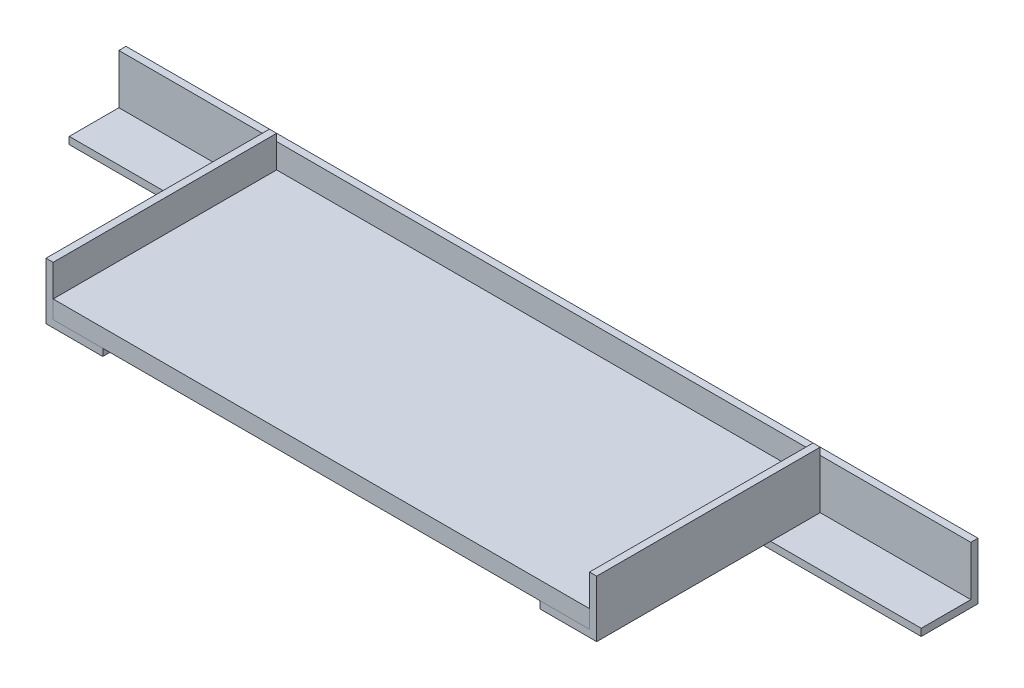
SolidWorks part; units mm, degrees
ref_plane "Front Plane" through (0, 0, 0) normal (0, 0, 1) x (1, 0, 0)
ref_plane "Top Plane" through (0, 0, 0) normal (0, 1, 0) x (1, 0, 0)
ref_plane "Right Plane" through (0, 0, 0) normal (1, 0, 0) x (0, 0, -1)
sketch "Bounding Box" plane through (0, 0, 0) normal (0, 1, 0) x (1, 0, 0)
  line L0 (0, -54.1882) -> (0, 0) construction
  line L1 (100, -179.1882) -> (-100, -179.1882)
  line L2 (100, -179.1882) -> (100, 70.8118)
  line L3 (100, 70.8118) -> (-100, 70.8118)
  line L4 (-100, -179.1882) -> (-100, 70.8118)
  line L5 (100, -179.1882) -> (-100, 70.8118) construction
  line L6 (100, 70.8118) -> (-100, -179.1882) construction
  dimension "D1" = 250
  dimension "D2" = 200
sketch "Sketch2" plane through (0, 0, 0) normal (0, 1, 0) x (1, 0, 0)
  line L4 (0, 39.3098) -> (0, -179.1882) construction
  line L6 (100, -179.1882) -> (-100, -179.1882) construction
  line L8 (-66.6, 34.925) -> (-92, 34.925)
  line L9 (-66.6, 34.925) -> (-66.6, -34.925)
  line L10 (-66.6, -34.925) -> (-92, -34.925)
  line L11 (-92, 34.925) -> (-92, -34.925)
  line L12 (-66.6, 34.925) -> (-92, -34.925) construction
  line L13 (-66.6, -34.925) -> (-92, 34.925) construction
  line L19 (-100, -179.1882) -> (-100, 70.8118) construction
  line L20 (-55.7, 39.3098) -> (-55.7, -40.925)
  line L21 (-60, -68.1179) -> (-60, -118.1179)
  line L22 (-55.7, -40.925) -> (-55, -40.925)
  line L23 (-55, 39.3098) -> (-55, -40.925)
  line L24 (-55, -40.925) -> (-55, -42.925)
  line L25 (-55, -42.925) -> (-96, -42.925)
  line L26 (-96, 47.7081) -> (-96, -50.925)
  line L27 (-91.789, -68.1179) -> (91.789, -68.1179)
  line L28 (-91.789, -68.1179) -> (-91.789, -198.1179)
  line L29 (-91.789, -198.1179) -> (91.789, -198.1179)
  line L30 (91.789, -68.1179) -> (91.789, -198.1179)
  line L31 (-91.789, -68.1179) -> (91.789, -198.1179) construction
  line L32 (-91.789, -198.1179) -> (91.789, -68.1179) construction
  line L33 (-55, 13) -> (-10, 13)
  line L34 (-55, 13) -> (-55, -13)
  line L35 (-55, -13) -> (-10, -13)
  line L36 (-10, 13) -> (-10, -13)
  line L37 (-60, -118.1179) -> (60, -118.1179)
  line L38 (60, -118.1179) -> (60, -68.1179)
  line L41 (-96, -50.925) -> (-100, -50.925)
  line L43 (-96, 47.7081) -> (-100, 47.7081)
  line L44 (-100, 47.7081) -> (-100, -50.925)
  line L45 (-55.7, 0) -> (-10, 0) construction
  line L46 (-95.3, -50.925) -> (-95.3, -42.925)
  line L47 (-96, -50.925) -> (0, -50.925)
  line L48 (-55.7, 39.3098) -> (0, 39.3098)
  line L49 (0, 39.3098) -> (0, -50.925)
  circle A0 centre (74.0462, -90.8108) radius 12.5
  circle A1 centre (-77.6221, -84.4915) radius 12.5
  point P0 (-79.3, 0)
  point P6 (-10, 0)
  point P15 (79.3, 0)
  point P27 (0, -133.1179)
  point P44 (0, -118.1179)
  point P49 (-79.3, 11.3081)
  point P52 (-55, 125)
  dimension "D16" = 25
  dimension "D17" = 45
  dimension "D1" = 69.85
  dimension "D2" = 25.4
  dimension "D3" = 8
  dimension "D4" = 6
  dimension "D5" = 16
  dimension "D6" = 0.7
  dimension "D7" = 4
  dimension "D8" = 2
  dimension "D9" = 120
  dimension "D10" = 0.7
  dimension "D11" = 130
  dimension "D12" = 45
  dimension "D13" = 26
  dimension "D14" = 50
extrude "Platform" add sketch "Sketch2" against normal blind 4 from offset 18 separate body contours L37 L38 L27 L21 region at (0, 0, 93.1179)
sketch "Sketch3" plane through (0, 0, 0) normal (1, 0, 0) x (0, 0, -1)
  line L0 (-68.1179, 23.5) -> (-68.1179, 12.4)
  line L1 (-68.1179, 12.4) -> (-79.2179, 12.4)
  line L2 (-79.2179, 12.4) -> (-79.2179, 10.8)
  line L3 (-79.2179, 10.8) -> (-66.5179, 10.8)
  line L4 (-66.5179, 10.8) -> (-66.5179, 23.5)
  line L5 (-66.5179, 23.5) -> (-68.1179, 23.5)
  line L7 (-68.1179, 14) -> (-68.1179, 18) construction
  line L8 (-118.1179, 14) -> (-68.1179, 14) construction
  dimension "D1" = 1.6
  dimension "D2" = 12.7
  dimension "D3" = 1.6
extrude "Alu Angle Platform Rest" add sketch "Sketch3" along normal mid plane 190.6 separate body
sketch "Drive Axle Holes" plane through (0, 0, 0) normal (1, 0, 0) x (0, 0, -1)
  line L0 (0, 0) -> (0, 50.8) construction
  line L1 (13, 0) -> (-13, 0) construction
  line L2 (10, 50.8) -> (-10, 50.8) construction
  circle A0 centre (0, 50.8) radius 7
  circle A1 centre (0, 50.8) radius 5
  point P4 (0, 0)
  point P8 (0, 50.8)
  dimension "D3" = 14
  dimension "D4" = 10
  dimension "D1" = 50.8
  dimension "D2" = 20
sketch "Sketch8" plane through (0, 0, 118.1179) normal (0, 0, 1) x (1, 0, 0)
  line L0 (-48.9, 12.4) -> (-61.6, 12.4)
  line L2 (-61.6, 12.4) -> (-61.6, 25.1)
  line L3 (-60, 14) -> (-60, 18) construction
  line L4 (-61.6, 25.1) -> (-60, 25.1)
  line L5 (-60, 25.1) -> (-60, 14)
  line L6 (-60, 14) -> (-48.9, 14)
  line L7 (-48.9, 14) -> (-48.9, 12.4)
  line L8 (-60, 14) -> (60, 14) construction
  dimension "D1" = 12.7
  dimension "D2" = 1.6
extrude "Platform Angle RH" add sketch "Sketch8" against normal up to surface (50 mm away) separate body up to face at (0, 17.95, 68.1179)
mirror "Platform Angle LH" about plane through (0, 0, 0) normal (1, 0, 0) of bodies 110
sketch "Sketch16" plane through (0, 0, 0) normal (0, 1, 0) x (1, 0, 0)
  line L0 (-77.3, -66.5179) -> (-64.6, -66.5179)
  line L1 (95.3, -66.5179) -> (-95.3, -66.5179) construction
  line L2 (-64.6, -66.5179) -> (-64.6, -79.2179)
  line L3 (-64.6, -79.2179) -> (-66.2, -79.2179)
  line L4 (-66.2, -79.2179) -> (-66.2, -68.1179)
  line L5 (-66.2, -68.1179) -> (-77.3, -68.1179)
  line L6 (-77.3, -68.1179) -> (-77.3, -66.5179)
  line L8 (-61.6, -68.1179) -> (-61.6, -118.1179) construction
  dimension "D1" = 12.7
  dimension "D2" = 1.6
  dimension "D3" = 3
